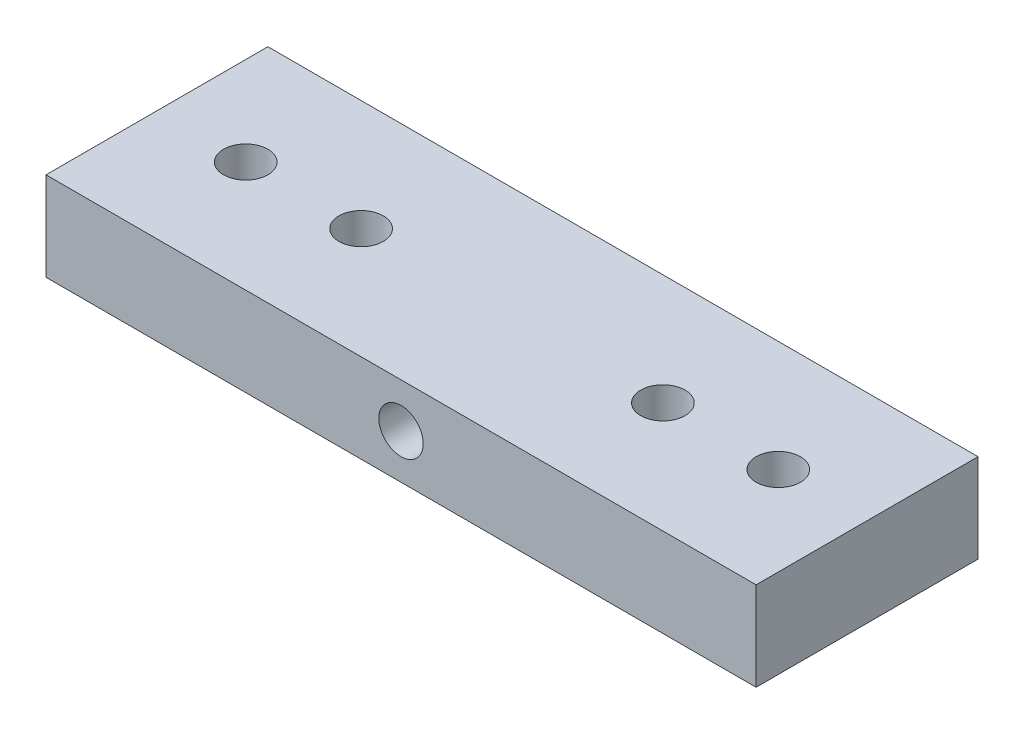
SolidWorks part; units mm, degrees
ref_plane "Front Plane" through (0, 0, 0) normal (0, 0, 1) x (1, 0, 0)
ref_plane "Top Plane" through (0, 0, 0) normal (0, 1, 0) x (1, 0, 0)
ref_plane "Right Plane" through (0, 0, 0) normal (1, 0, 0) x (0, 0, -1)
sketch "Sketch1" plane through (0, 0, 0) normal (0, 1, 0) x (1, 0, 0)
  line L0 (19.386, 0) -> (19.386, 31.75) construction
  line L1 (-31.414, 0) -> (70.186, 0)
  line L2 (-31.414, 0) -> (-31.414, 31.75)
  line L3 (-31.414, 31.75) -> (70.186, 31.75)
  line L4 (70.186, 0) -> (70.186, 31.75)
  circle A0 centre (-18.714, 15.875) radius 3.175
  circle A1 centre (57.486, 15.875) radius 3.175
  circle A3 centre (-2.204, 15.875) radius 3.175
  circle A4 centre (40.976, 15.875) radius 3.175
  point P8 (-31.414, 15.875)
  dimension "D3" = 6.35
  dimension "D4" = 38.1
  dimension "D5" = 6.35
  dimension "D6" = 21.59
  dimension "D1" = 101.6
  dimension "D2" = 31.75
extrude "Boss-Extrude1" add sketch "Sketch1" along normal blind 12.7
sketch "Sketch3" plane through (0, 0, 0) normal (0, 0, 1) x (1, 0, 0)
  line L0 (-31.414, 12.7) -> (-31.414, 0) construction
  line L1 (-31.414, 0) -> (70.186, 0) construction
  circle A0 centre (19.386, 6.35) radius 3.175
  dimension "D1" = 6.35
  dimension "D3" = 6.35
  dimension "D2" = 50.8
extrude "Cut-Extrude1" cut sketch "Sketch3" against normal blind 25.4
